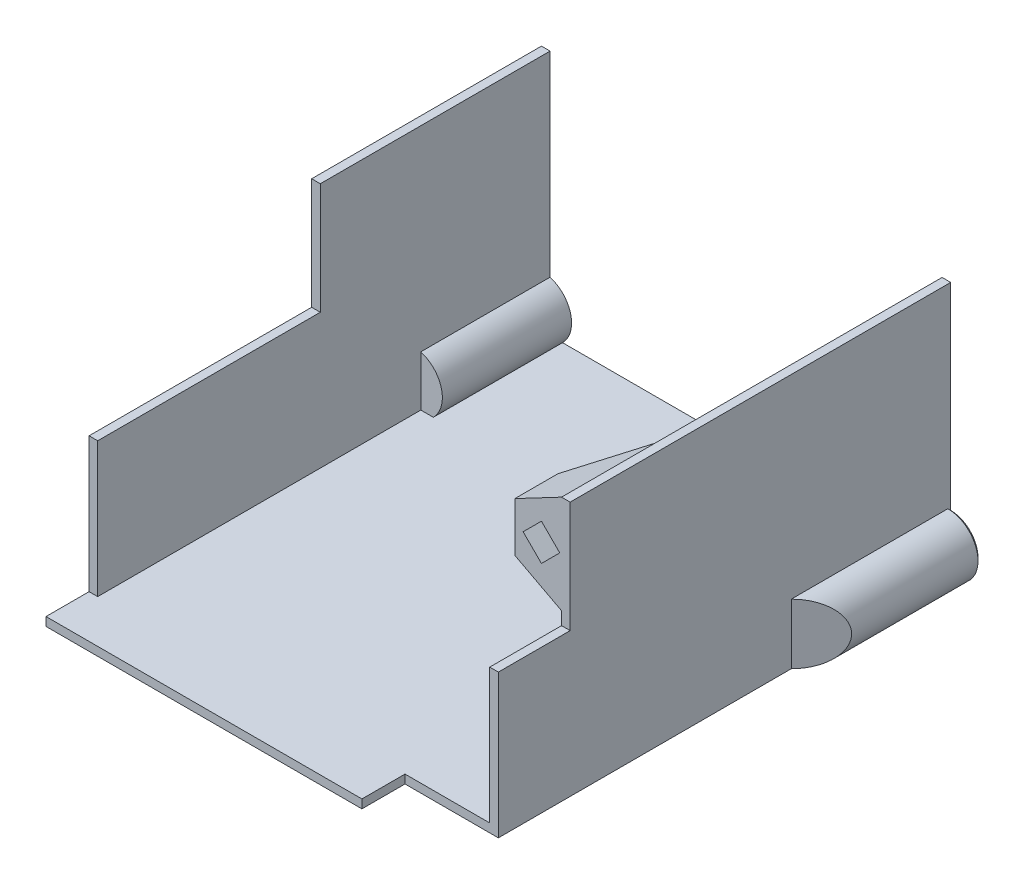
SolidWorks part; units mm, degrees
material "Custom Plastic"
ref_plane "Front Plane" through (0, 0, 0) normal (0, 0, 1) x (1, 0, 0)
ref_plane "Top Plane" through (0, 0, 0) normal (0, 1, 0) x (1, 0, 0)
ref_plane "Right Plane" through (0, 0, 0) normal (1, 0, 0) x (0, 0, -1)
sketch "Sketch1" plane through (0, 0, 0) normal (0, 0, 1) x (1, 0, 0)
  line L1 (-33.6475, 14.5475) -> (-34.8475, 14.5475)
  line L2 (-33.6475, -19.7525) -> (-33.6475, -20.9525) construction
  line L3 (-31.9081, -19.7525) -> (19.2131, -19.7525)
  line L4 (20.9525, 14.5475) -> (20.9525, -12.7276)
  line L5 (-33.6475, -12.7276) -> (-33.6475, 14.5475)
  line L7 (20.9525, 14.5475) -> (22.1525, 14.5475)
  line L8 (-34.8475, 14.5475) -> (-34.8475, -12.5525)
  line L9 (-34.8475, -20.9525) -> (22.1525, -20.9525)
  line L10 (22.1525, 14.5475) -> (22.1525, -12.5525)
  arc A0 (22.1525, -20.9525) -> (22.1525, -12.5525) centre (22.1525, -16.7525) ccw
  circle A1 centre (22.1525, -16.7525) radius 1.6 construction
  arc A2 (20.9525, -12.7276) -> (19.2131, -19.7525) centre (22.1525, -16.7525) ccw
  circle A3 centre (-34.8475, -16.7525) radius 1.6 construction
  arc A4 (-34.8475, -12.5525) -> (-34.8475, -20.9525) centre (-34.8475, -16.7525) ccw
  arc A6 (-31.9081, -19.7525) -> (-33.6475, -12.7276) centre (-34.8475, -16.7525) ccw
  dimension "D2" = 3.2
  dimension "D5" = 4.2
  dimension "D1" = 1.2
  dimension "D3" = 57
  dimension "D4" = 35.5
extrude "Boss-Extrude1" add sketch "Sketch1" along normal blind 69
sketch "Sketch2" plane through (0, 0, 69) normal (0, 0, 1) x (1, 0, 0)
  line L0 (-34.8475, -20.9525) -> (22.1525, -20.9525) construction
  line L1 (9.1525, -20.9525) -> (32.8781, -20.9525)
  line L2 (9.1525, -20.9525) -> (9.1525, -19.7525)
  line L3 (-34.8475, 12.6741) -> (32.8781, 12.6741)
  line L4 (32.8781, -20.9525) -> (32.8781, 12.6741)
  line L5 (22.1525, -12.5525) -> (22.1525, 14.5475) construction
  line L6 (9.1525, -19.7525) -> (-34.8475, -19.7525)
  line L7 (19.2131, -19.7525) -> (-31.9081, -19.7525) construction
  line L8 (-34.8475, 14.5475) -> (-34.8475, -12.5525) construction
  line L9 (-34.8475, -20.9525) -> (-34.8475, -19.7525)
  line L10 (-34.8475, -20.9525) -> (-42.7406, -20.9525)
  line L11 (-34.8475, -20.9525) -> (22.1525, -20.9525) construction
  line L12 (-42.7406, -20.9525) -> (-42.7406, -7.5075)
  line L13 (-42.7406, -7.5075) -> (-34.8475, -7.5075)
  line L14 (-34.8475, -7.5075) -> (-34.8475, 12.6741)
  dimension "D1" = 13
extrude "Cut-Extrude1" cut sketch "Sketch2" against normal blind 6
sketch "Sketch3" plane through (0, 0, 63) normal (0, 0, 1) x (1, 0, 0)
  line L0 (22.1525, -12.5525) -> (22.1525, 12.6741) construction
  line L1 (-34.8475, 14.5475) -> (22.1525, 14.5475)
  line L2 (-34.8475, 14.5475) -> (-34.8475, -0.9525)
  line L3 (-34.8475, -0.9525) -> (22.1525, -0.9525)
  line L4 (22.1525, 14.5475) -> (22.1525, -0.9525)
  dimension "D1" = 15.5
extrude "Cut-Extrude2" cut sketch "Sketch3" against normal blind 10 and the other way blind 10
sketch "Sketch4" plane through (0, 0, 53) normal (0, 0, 1) x (1, 0, 0)
  line L0 (-34.8475, 14.5475) -> (-34.8475, -0.9525) construction
  line L1 (-34.8475, 14.5475) -> (-33.6475, 14.5475)
  line L2 (-34.8475, 14.5475) -> (-34.8475, -0.9525)
  line L3 (-34.8475, -0.9525) -> (-33.6475, -0.9525)
  line L4 (-33.6475, 14.5475) -> (-33.6475, -0.9525)
extrude "Cut-Extrude3" cut sketch "Sketch4" against normal blind 21
sketch "Sketch6" plane through (0, 0, 0) normal (0, 0, -1) x (-1, 0, 0)
  circle A0 centre (-22.1525, -16.7525) radius 1.6
  circle A1 centre (34.8475, -16.7525) radius 1.6
  arc A2 (34.8475, -20.9525) -> (34.8475, -12.5525) centre (34.8475, -16.7525) ccw construction
  arc A3 (-22.1525, -12.5525) -> (-22.1525, -20.9525) centre (-22.1525, -16.7525) ccw construction
  dimension "D1" = 3.2
extrude "Cut-Extrude4" cut sketch "Sketch6" against normal blind 16
sketch "Sketch7" plane through (0, 0, 63) normal (0, 0, 1) x (1, 0, 0)
  line L0 (19.2131, -19.7525) -> (9.1525, -19.7525) construction
  line L1 (22.1525, -12.5525) -> (31.8181, -12.5525)
  line L2 (22.1525, -12.5525) -> (22.1525, -20.9525)
  line L3 (22.1525, -20.9525) -> (31.8181, -20.9525)
  line L4 (31.8181, -12.5525) -> (31.8181, -20.9525)
  line L5 (20.9525, -12.7276) -> (15.0843, -12.7276)
  line L6 (20.9525, -12.7276) -> (20.9525, -19.7525)
  line L7 (20.9525, -19.7525) -> (15.0843, -19.7525)
  line L8 (15.0843, -12.7276) -> (15.0843, -19.7525)
  line L9 (-33.6475, -12.7276) -> (-33.6475, -0.9525) construction
  line L10 (-34.8475, -20.9525) -> (-44.0251, -20.9525)
  line L11 (-34.8475, -20.9525) -> (-34.8475, -7.6032)
  line L12 (-34.8475, -7.6032) -> (-44.0251, -7.6032)
  line L13 (-44.0251, -20.9525) -> (-44.0251, -7.6032)
  line L14 (-33.6475, -7.6032) -> (-26.816, -7.6032)
  line L15 (-33.6475, -7.6032) -> (-33.6475, -19.7525)
  line L16 (-33.6475, -19.7525) -> (-26.816, -19.7525)
  line L17 (-26.816, -7.6032) -> (-26.816, -19.7525)
  line L18 (9.1525, -19.7525) -> (-34.8475, -19.7525) construction
extrude "Cut-Extrude5" cut sketch "Sketch7" against normal offset from surface (45 mm away) 18 up to face at (-36.4475, -16.7525, 0)
chamfer "Chamfer1" distance 4.2 angle 45 2 edges at (22.1525, -16.7525, 18) (-34.8475, -16.7525, 18)
chamfer "Chamfer3" distance 0.6 angle 30 2 edges at (20.5525, -16.7525, 0) (-36.4475, -16.7525, 0) first distance on face at (20.5525, -16.7525, 16) first distance on face at (-36.4475, -16.7525, 16)
chamfer "Chamfer4" distance 0.4 angle 45 3 edges at (-39.0475, -16.7525, 0) (-6.3475, -20.9525, 0) (26.3525, -16.7525, 0)
sketch "Sketch8" plane through (0, 0, 53) normal (0, 0, 1) x (1, 0, 0)
  line L0 (18.1525, 9.2975) -> (14.4525, 9.2975) construction
  line L1 (15.6025, 7.6975) -> (18.1525, 10.2475)
  line L2 (14.4525, 6.0975) -> (18.1525, 6.0975) construction
  line L4 (14.4525, 11.1225) -> (14.4525, 9.2975)
  line L5 (14.4525, 6.0975) -> (14.4525, 4.2725)
  line L7 (20.9525, 14.5475) -> (20.9525, -0.9525) construction
  line L8 (20.9525, 0.8475) -> (22.1525, 0.8475)
  line L9 (22.1525, -0.9525) -> (22.1525, 14.5475) construction
  line L10 (22.1525, 0.8475) -> (22.1525, 14.5475)
  line L11 (22.1525, 14.5475) -> (20.9525, 14.5475)
  line L12 (15.6025, 7.6975) -> (18.1525, 5.1475)
  line L13 (18.1525, 10.2475) -> (20.7025, 7.6975)
  line L14 (18.1525, 5.1475) -> (20.7025, 7.6975)
  line L15 (15.6025, 7.6975) -> (20.7025, 7.6975) construction
  line L16 (18.1525, 10.2475) -> (18.1525, 5.1475) construction
  line L17 (14.4525, 9.2975) -> (14.4525, 6.0975)
  line L18 (20.9525, 14.5475) -> (14.4525, 11.1225)
  line L19 (20.9525, 0.8475) -> (14.4525, 4.2725)
  arc A0 (18.1525, 6.0975) -> (18.1525, 9.2975) centre (18.1525, 7.6975) ccw construction
  circle A1 centre (18.1525, 7.6975) radius 2.55 construction
  dimension "D1" = 1.6
  dimension "D5" = 5.1
  dimension "D2" = 2.8
  dimension "D3" = 6.85
  dimension "D4" = 6.5
  dimension "D6" = 6.85
extrude "Boss-Extrude2" add sketch "Sketch8" against normal blind 13
sketch "Sketch10" plane through (0, 0, 40) normal (0, 0, -1) x (-1, 0, 0)
  line L0 (-18.1525, 10.6975) -> (-14.4525, 10.6975)
  line L1 (-14.4525, 11.1225) -> (-14.4525, 4.2725) construction
  line L2 (-14.4525, 10.6975) -> (-14.4525, 4.6975)
  line L3 (-14.4525, 4.6975) -> (-18.1525, 4.6975)
  line L5 (-18.1525, 10.2475) -> (-18.1525, 5.1475) construction
  arc A0 (-18.1525, 10.6975) -> (-18.1525, 4.6975) centre (-18.1525, 7.6975) ccw
  arc A1 (-18.1525, 4.6975) -> (-18.1525, 10.6975) centre (-18.1525, 7.6975) ccw construction
  dimension "D1" = 3
extrude "Cut-Extrude6" cut sketch "Sketch10" against normal offset from surface 6 and the other way blind 10 up to face at (19.4382, 6.2046, 53)
sketch "Sketch11" plane through (0, 14.5475, 0) normal (0, 1, 0) x (1, 0, 0)
  line L0 (20.9525, -40) -> (14.4525, -47)
  line L1 (14.4525, -40) -> (14.4525, -53) construction
  line L2 (14.4525, -47) -> (14.4525, -40)
  line L3 (14.4525, -40) -> (20.9525, -40)
extrude "Cut-Extrude7" cut sketch "Sketch11" against normal up to surface (10.275 mm away) up to face at (17.7025, 2.56, 46.5)
